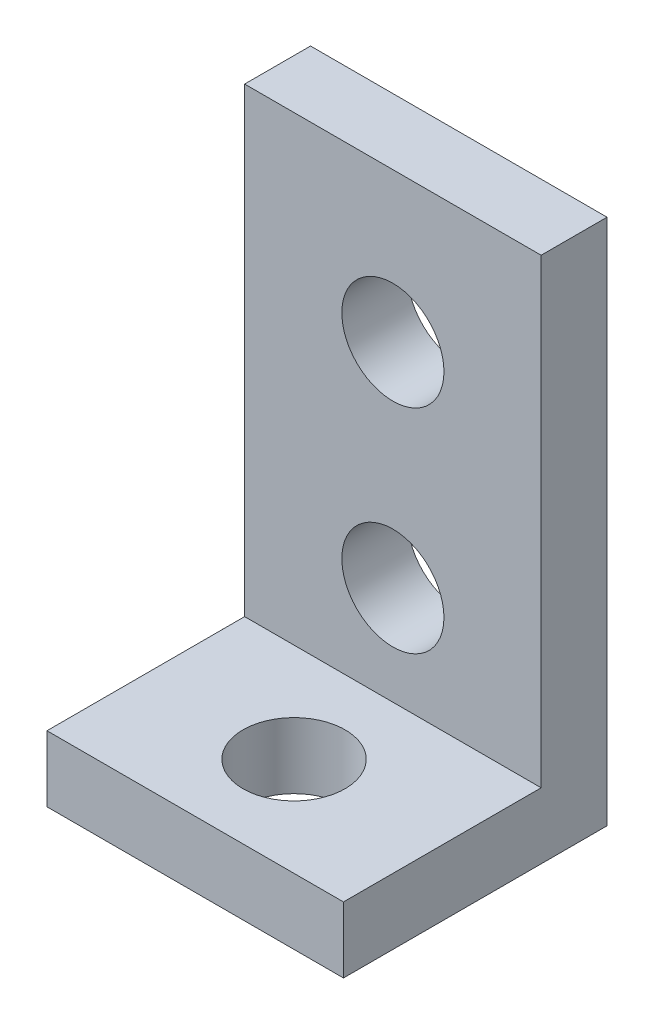
SolidWorks part; units mm, degrees
ref_plane "前视基准面" through (0, 0, 0) normal (0, 0, 1) x (1, 0, 0)
ref_plane "上视基准面" through (0, 0, 0) normal (0, 1, 0) x (1, 0, 0)
ref_plane "右视基准面" through (0, 0, 0) normal (1, 0, 0) x (0, 0, -1)
other "Configuration Table"
sketch "草图1" plane through (0, 0, 0) normal (1, 0, 0) x (0, 0, -1)
  line L0 (0, 0) -> (8, 0)
  line L1 (8, 0) -> (8, 16)
  line L2 (8, 16) -> (6, 16)
  line L3 (6, 16) -> (6, 2)
  line L4 (6, 2) -> (0, 2)
  line L5 (0, 2) -> (0, 0)
  dimension "D1" = 8
  dimension "D2" = 16
  dimension "D3" = 2
  dimension "D4" = 14
extrude "凸台-拉伸1" add sketch "草图1" along normal blind 9
sketch3d "3D草图2"
  line L0 (9, 2, 0) -> (0, 2, 0) construction
  line L2 (0, 2, -6) -> (0, 2, 0) construction
  circle A0 centre (4.5, 2, -3) radius 1.55
  point P13 (4.5, 3.55, -3)
  dimension "D1" = 3
  dimension "D2" = 4.5
extrude "切除-拉伸1" cut sketch "3D草图2" along direction (0, 1, 0) on the side against the normal through all
sketch3d "3D草图3"
  circle A0 centre (4.5, 11.4636, -8) radius 1.55
  circle A1 centre (4.5, 5.0016, -8) radius 1.55
  point P13 (4.5, 11.4636, -6.45)
  point P16 (4.5, 5.0016, -6.45)
extrude "切除-拉伸2" cut sketch "3D草图3" along direction (0, 0, -1) on the side against the normal through all
